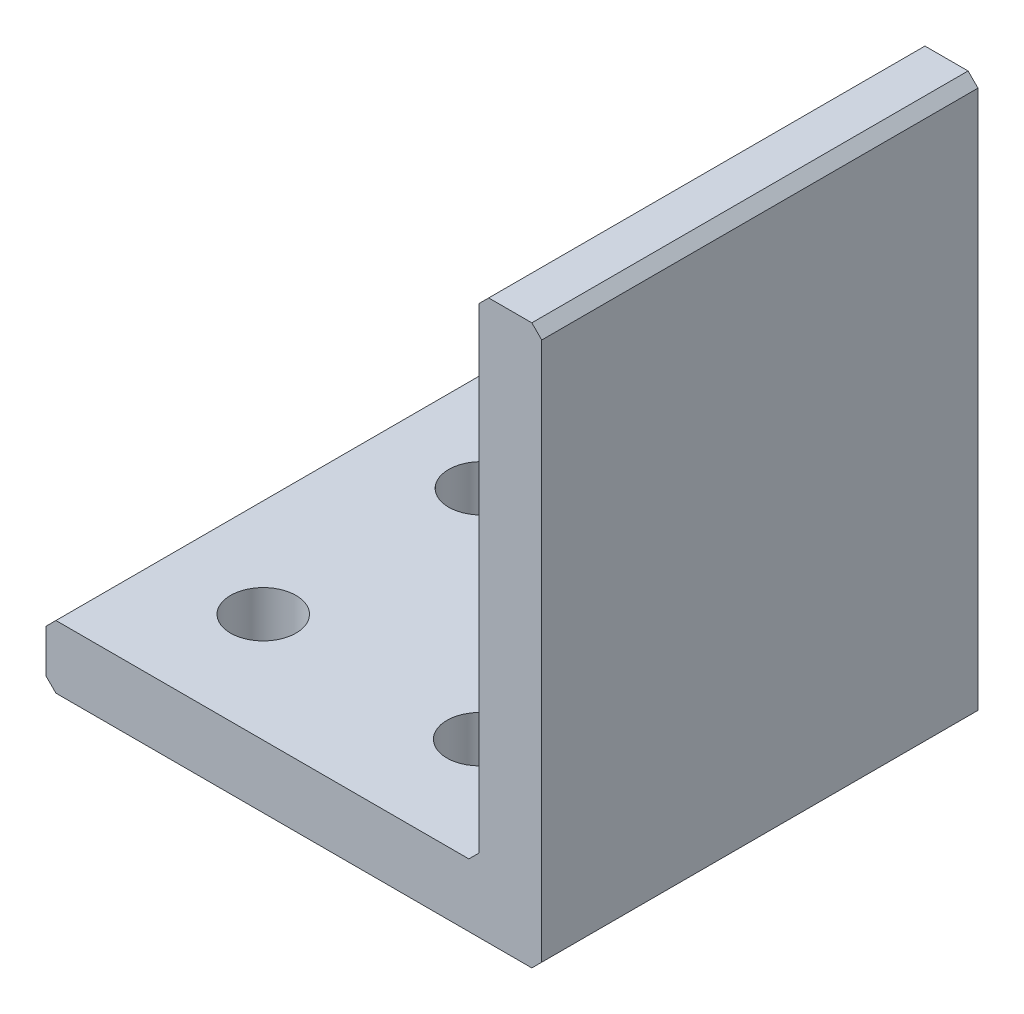
SolidWorks part; units mm, degrees
ref_plane "Front Plane" through (0, 0, 0) normal (0, 0, 1) x (1, 0, 0)
ref_plane "Top Plane" through (0, 0, 0) normal (0, 1, 0) x (1, 0, 0)
ref_plane "Right Plane" through (0, 0, 0) normal (1, 0, 0) x (0, 0, -1)
sketch "Sketch1" plane through (0, 0, 0) normal (0, 1, 0) x (1, 0, 0)
  line L1 (-12.5, -11) -> (12.5, -11)
  line L2 (-12.5, -11) -> (-12.5, 11)
  line L3 (-12.5, 11) -> (12.5, 11)
  line L4 (12.5, -11) -> (12.5, 11)
  line L5 (-12.5, -11) -> (12.5, 11) construction
  line L6 (-12.5, 11) -> (12.5, -11) construction
  point P0 (0, 0)
  dimension "D1" = 22
  dimension "D2" = 25
extrude "Boss-Extrude1" add sketch "Sketch1" along normal blind 3.175
sketch "Sketch3" plane through (0, 3.175, 0) normal (0, 1, 0) x (1, 0, 0)
  line L0 (-12.5, -11) -> (12.5, -11) construction
  line L1 (12.5, 11) -> (9.325, 11)
  line L2 (12.5, 11) -> (12.5, -11)
  line L3 (12.5, -11) -> (9.325, -11)
  line L4 (9.325, 11) -> (9.325, -11)
  dimension "D1" = 3.175
extrude "Boss-Extrude2" add sketch "Sketch3" along normal blind 25
sketch "Sketch5" plane through (0, 3.175, 0) normal (0, 1, 0) x (1, 0, 0)
  line L0 (-1.5875, 11) -> (-12.5, 11) construction
  line L1 (-1.5875, 11) -> (-1.5875, -11) construction
  line L2 (-12.5, -11) -> (9.325, -11) construction
  line L3 (-7.0438, 11) -> (-7.0438, -11) construction
  line L4 (-1.5875, 11) -> (9.325, 11) construction
  line L5 (3.8687, 11) -> (3.8688, -11) construction
  line L6 (-12.5, 0) -> (9.325, 0) construction
  line L7 (-12.5, 11) -> (-12.5, -11) construction
  line L8 (9.325, 11) -> (9.325, -11) construction
  line L9 (-12.5, 0) -> (-12.5, 11) construction
  line L10 (-12.5, 5.5) -> (9.325, 5.5) construction
  line L11 (-12.5, 0) -> (-12.5, -11) construction
  line L12 (-12.5, -5.5) -> (9.325, -5.5) construction
  line L13 (9.325, 11) -> (9.325, -11) construction
  circle A0 centre (-7.0438, 5.5) radius 1.65
  circle A1 centre (3.8688, 5.5) radius 1.65
  circle A2 centre (-7.0438, -5.5) radius 1.65
  circle A3 centre (3.8688, -5.5) radius 1.65
  dimension "D1" = 3.3
  dimension "D2" = 3.3
  dimension "D3" = 3.3
  dimension "D4" = 3.3
extrude "Cut-Extrude1" cut sketch "Sketch5" against normal through all
chamfer "Chamfer1" distance 0.5 angle 45 6 edges at (-12.5, 0, 0) (-12.5, 3.175, 0) (12.5, 28.175, 0) (9.325, 28.175, 0) (12.5, 0, 0) (9.325, 3.175, 0)
